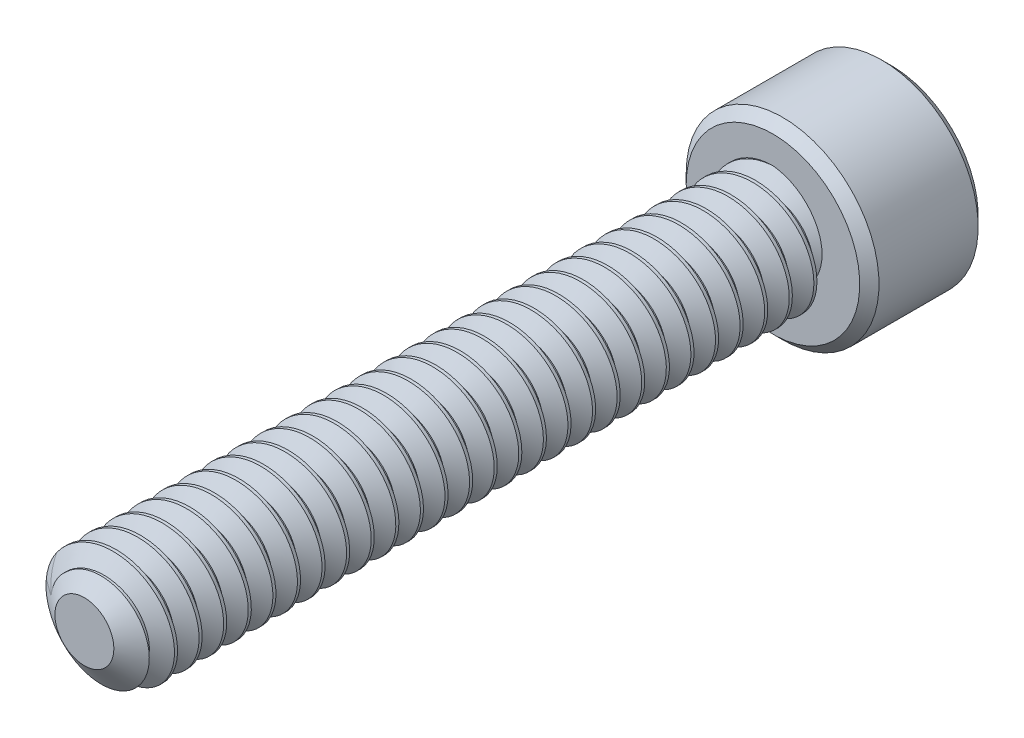
SolidWorks part; units mm, degrees
material "Alloy Steel"
ref_plane "Front Plane" through (0, 0, 0) normal (0, 0, 1) x (1, 0, 0)
ref_plane "Top Plane" through (0, 0, 0) normal (0, 1, 0) x (1, 0, 0)
ref_plane "Right Plane" through (0, 0, 0) normal (1, 0, 0) x (0, 0, -1)
sketch "Sketch1" plane through (0, 0, 0) normal (0, 0, 1) x (1, 0, 0)
  circle A0 centre (0, 0) radius 1.0922
  dimension "OD" = 2.1844
extrude "Extrude1" add sketch "Sketch1" against normal blind 12.7
sketch "Sketch2" plane through (0, 0, 0) normal (0, 0, 1) x (1, 0, 0)
  circle A0 centre (0, 0) radius 1.0922 construction
  circle A1 centre (0, 0) radius 1.0922
curve "Helix/Spiral1" pitch 0.4536 height 13.1536 radius 1.0922 centre (0, 0, 0) axis (0, 0, -1) start towards (0, 1, 0) parameters "pitch"=0.4536
sketch "Sketch3" plane through (0, 0, 0) normal (1, 0, 0) x (0, 0, -1)
  line L0 (-0.3969, 1.0922) -> (-0.2268, 0.7976)
  line L1 (-0.2268, 0.7976) -> (-0.1701, 0.7976)
  line L2 (-0.1701, 0.7976) -> (0, 1.0922)
  line L3 (-0.3969, 1.0922) -> (0, 1.0922)
  line L4 (-0.1984, 1.0922) -> (-0.1984, 0.7976) construction
  line L5 (-0.3118, 0.9449) -> (-0.085, 0.9449) construction
  line L6 (0, 1.0922) -> (0, -1.0922) construction
  dimension "D1" = 0.0567
  dimension "D2" = 0.2268
  dimension "D3" = 60
sweep "Cut-Sweep1" cut profiles "Sketch3" path "Helix/Spiral1"
sketch "Sketch4" plane through (0, 0, 0) normal (1, 0, 0) x (0, 0, -1)
  line L0 (0.3841, 1.0922) -> (0, 0.5436)
  line L1 (0, 0.5436) -> (0, 1.0922)
  line L2 (0.3841, 1.0922) -> (0, 1.0922)
  line L3 (-0.3969, 1.0922) -> (0, 1.0922) construction
  line L4 (0, 0) -> (7.0209, 0) construction
  dimension "D1" = 55
  dimension "D2" = 0.254
revolve "Cut-Revolve1" cut sketch "Sketch4" angle 360 about L4
sketch "Sketch5" plane through (0, 0, 0) normal (1, 0, 0) x (0, 0, -1)
  line L0 (12.7, -0.8061) -> (12.7, 0.7793) construction
  line L1 (12.7, 1.2192) -> (87.4665, 1.2192)
  line L2 (12.7, 1.2192) -> (12.7, 0)
  line L3 (12.7, 0) -> (87.3125, 0)
  line L4 (87.3125, 0.889) -> (87.3125, 0)
  line L5 (87.4665, 1.2192) -> (87.3125, 0.889)
  line L6 (0, 0) -> (9.9695, 0) construction
  point P3 (87.3125, 1.2192)
  point P10 (87.3125, 1.2192)
  dimension "D1" = 0.3302
  dimension "Thread min" = 87.3125
  dimension "D2" = 0.127
  dimension "D3" = 25
revolve "partially thread" [suppressed] add sketch "Sketch5" angle 360 about L6
sketch "Sketch6" plane through (0, 0, -12.7) normal (0, 0, -1) x (-1, 0, 0)
  circle A0 centre (0, 0) radius 1.778
  dimension "head dia" = 3.556
extrude "Extrude2" add sketch "Sketch6" along normal blind 2.1844
sketch "Sketch7" plane through (0, 0, -14.8844) normal (0, 0, -1) x (-1, 0, 0)
  line L1 (0, 1.1457) -> (-0.9922, 0.5728)
  line L2 (-0.9922, 0.5728) -> (-0.9922, -0.5728)
  line L3 (-0.9922, -0.5728) -> (0, -1.1457)
  line L4 (0, -1.1457) -> (0.9922, -0.5728)
  line L5 (0.9922, -0.5728) -> (0.9922, 0.5728)
  line L6 (0.9922, 0.5728) -> (0, 1.1457)
  circle A0 centre (0, 0) radius 0.9922 construction
  dimension "hex dia" = 1.9844
extrude "Cut-Extrude1" cut sketch "Sketch7" against normal blind 1.4883
sketch "Sketch8" plane through (0, 0, -14.8844) normal (0, 0, -1) x (-1, 0, 0)
  circle A0 centre (0, 0) radius 1.1457
extrude "Cut-Extrude2" cut sketch "Sketch8" against normal through all draft 45
chamfer "Chamfer1" distance 0.1778 angle 45 2 edges at (-1.778, 0, -14.8844) (-1.778, 0, -12.7)
sketch "Sketch9" plane through (0, 0, 0) normal (1, 0, 0) x (0, 0, -1)
  line L0 (0, 1.0922) -> (0, -1.0922) construction
  line L1 (2.4946, 1.0922) -> (2.4946, -1.0922) construction
  dimension "D1" = 2.4946
  dimension "D4" = 0.635
  dimension "D5" = 0.3302
equation "\"D3@Helix/Spiral1\" = \"screw length@Extrude1\"+\"pitch@Helix/Spiral1\""
equation "\"D1@Sketch3\" = \"pitch@Helix/Spiral1\"*.125"
equation "\"D2@Sketch3\" = \"pitch@Helix/Spiral1\"*.5"
equation "\"D1@Cut-Extrude1\" = \"hex dia@Sketch7\"*.75"
equation "\"D1@Chamfer1\" = \"head dia@Sketch6\"*.05"
equation "\"D1@Sketch9\" = \"pitch@Helix/Spiral1\"*5.5"
